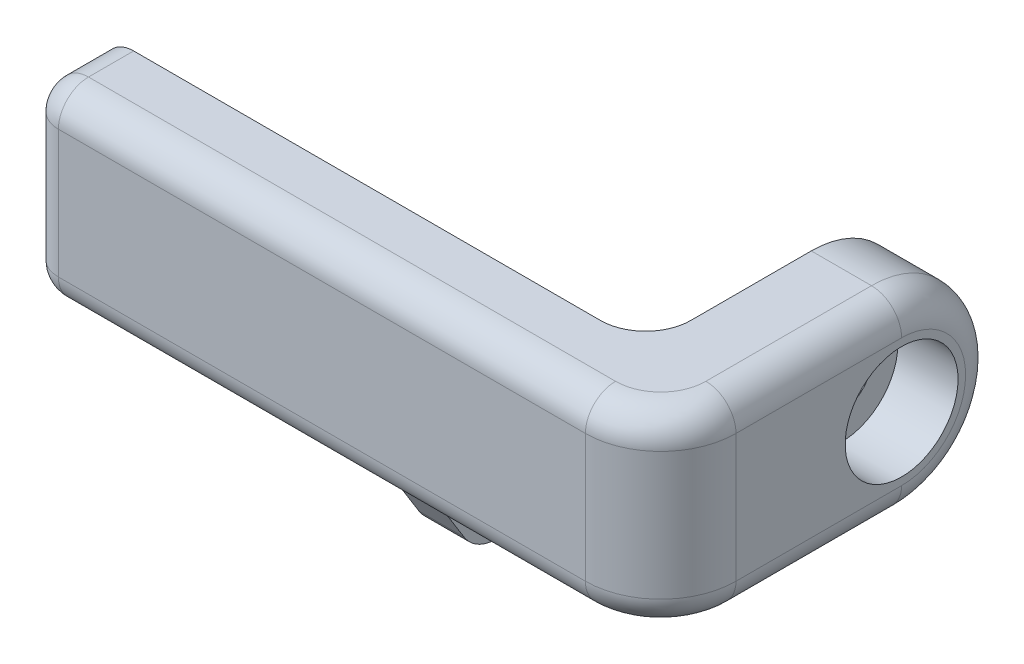
SolidWorks part; units mm, degrees
note: The reader was unsure of these and kept them because the rebuilt part matched: shared geometry of "Sketch1<3>", "Sketch3<6>".
ref_plane "Front Plane" through (0, 0, 0) normal (0, 0, 1) x (1, 0, 0)
ref_plane "Top Plane" through (0, 0, 0) normal (0, 1, 0) x (1, 0, 0)
ref_plane "Right Plane" through (0, 0, 0) normal (1, 0, 0) x (0, 0, -1)
sketch "Sketch1" plane through (0, 0, 0) normal (1, 0, 0) x (0, 0, -1)
  circle A0 centre (0, 0) radius 4
  circle A1 centre (0, 0) radius 12.5
  circle A2 centre (0, 0) radius 7.5
  dimension "D1" = 8
  dimension "D2" = 25
  dimension "D3" = 15
extrude "Boss-Extrude1" add sketch "Sketch1" along normal blind 12 contours A1 A2
extrude "Boss-Extrude2" add sketch "Sketch1<3>" along normal blind 4 contours A2 A0
sketch "Sketch1<3>" plane through (0, 0, 0) normal (1, 0, 0) x (0, 0, -1) same geometry as "Sketch1"
sketch "Sketch2" plane through (0, 0, 0) normal (0, 0, 1) x (1, 0, 0)
  line L0 (0, -13.75) -> (0, 13.75) construction
  line L1 (0, -12.5) -> (12, -12.5)
  line L2 (0, -12.5) -> (0, 12.5)
  line L3 (0, 12.5) -> (12, 12.5)
  line L4 (12, -12.5) -> (12, 12.5)
  line L5 (0, -12.5) -> (12, -12.5) construction
  point P9 (0, -12.5)
extrude "Boss-Extrude3" add sketch "Sketch2" along normal blind 32
sketch "Sketch3" plane through (12, 0, -12) normal (-1, 0, 0) x (0, 0, 1)
  circle A0 centre (12, 0) radius 4
  circle A1 centre (12, 0) radius 12.5
  circle A2 centre (12, 0) radius 7.5
  point P5 (12, 0)
  line M5 (12, -7.5) -> (12, 7.5)
  dimension "D1" = 8
  dimension "D2" = 25
  dimension "D3" = 15
extrude "Cut-Extrude1" cut sketch "Sketch3" along normal blind 8 contours A2 A0 M5
extrude "Cut-Extrude2" cut sketch "Sketch3<6>" along normal through all contours A0 M5
sketch "Sketch3<6>" plane through (12, 0, -12) normal (-1, 0, 0) x (0, 0, 1) same geometry as "Sketch3"
sketch "Sketch4" plane through (0, 0, 0) normal (-1, 0, 0) x (0, 0, 1)
  line L0 (32, -12.5) -> (0, -12.5) construction
  line L1 (32, 12.5) -> (22, 12.5)
  line L2 (32, 12.5) -> (32, -12.5)
  line L3 (32, -12.5) -> (22, -12.5)
  line L4 (22, 12.5) -> (22, -12.5)
  dimension "D1" = 10
extrude "Boss-Extrude4" add sketch "Sketch4" along normal blind 72
fillet "Fillet1" radius 6 1 edges at (0, 0, 22)
fillet "Fillet2" radius 10 1 edges at (12, 0, 32)
fillet "Fillet3" radius 4 10 edges at (-35, 12.5, 32) (9.0711, 12.5, 29.0711) (-35, -12.5, 32) (9.0711, -12.5, 29.0711) (12, -12.5, 11) (12, 0, -12.5) (-72, -12.5, 27) (-72, 12.5, 27) (-72, 0, 32) (12, 12.5, 11)
sketch "Sketch5" plane through (0, 0, 22) normal (0, 0, -1) x (-1, 0, 0)
  line L0 (0, 13.75) -> (0, -13.75) construction
  line L1 (23, 0) -> (29, 0)
  line L2 (23, 0) -> (23, -30.0781)
  line L3 (23, -30.0781) -> (29, -30.0781)
  line L4 (29, 0) -> (29, -30.0781)
  line L5 (24.475, 0) -> (-24.475, 0) construction
  point P6 (23, 0)
  dimension "D1" = 6
  dimension "D2" = 23
extrude "Boss-Extrude5" add sketch "Sketch5" along normal blind 35
sketch "Sketch6" plane through (-29, 0, 0) normal (-1, 0, 0) x (0, 0, 1)
  line L0 (-4.6274, -30.0781) -> (14.0601, 0)
  line L1 (-13, -30.0781) -> (22, -30.0781) construction
  line L2 (-76.2946, -145.4286) -> (10.0908, -6.3888) construction
  line L3 (-13, 0) -> (22, 0) construction
  line L4 (14.0601, 0) -> (-13, 0)
  line L5 (-13, 0) -> (-13, -30.0781)
  line L6 (-13, -30.0781) -> (-4.6274, -30.0781)
extrude "Cut-Extrude3" cut sketch "Sketch6" against normal up to next
sketch "Sketch7" plane through (0, 0, 22) normal (0, 0, 1) x (1, 0, 0)
  line L1 (-29, -12.5) -> (-23, -12.5)
  line L2 (-29, -12.5) -> (-29, -30.0781)
  line L3 (-29, -30.0781) -> (-23, -30.0781)
  line L4 (-23, -12.5) -> (-23, -30.0781)
extrude "Boss-Extrude6" add sketch "Sketch7" along normal up to vertex (6 mm away)
sketch "Sketch8" plane through (-29, 0, 0) normal (-1, 0, 0) x (0, 0, 1)
  line L0 (28, -12.5) -> (21.6434, -22.7311)
  line L1 (21.6434, -22.7311) -> (-0.0627, -22.7311)
  line L2 (-4.6274, -30.0781) -> (14.0601, 0) construction
  line L3 (-0.0627, -22.7311) -> (-4.6274, -30.0781)
  line L4 (-4.6274, -30.0781) -> (28, -30.0781)
  line L5 (28, -30.0781) -> (28, -12.5)
extrude "Cut-Extrude4" cut sketch "Sketch8" against normal up to next
fillet "Fillet4" radius 5 3 edges at (-26, -22.7311, 21.6434) (-26, -22.7311, -0.0627) (-26, 0, 14.0601)
